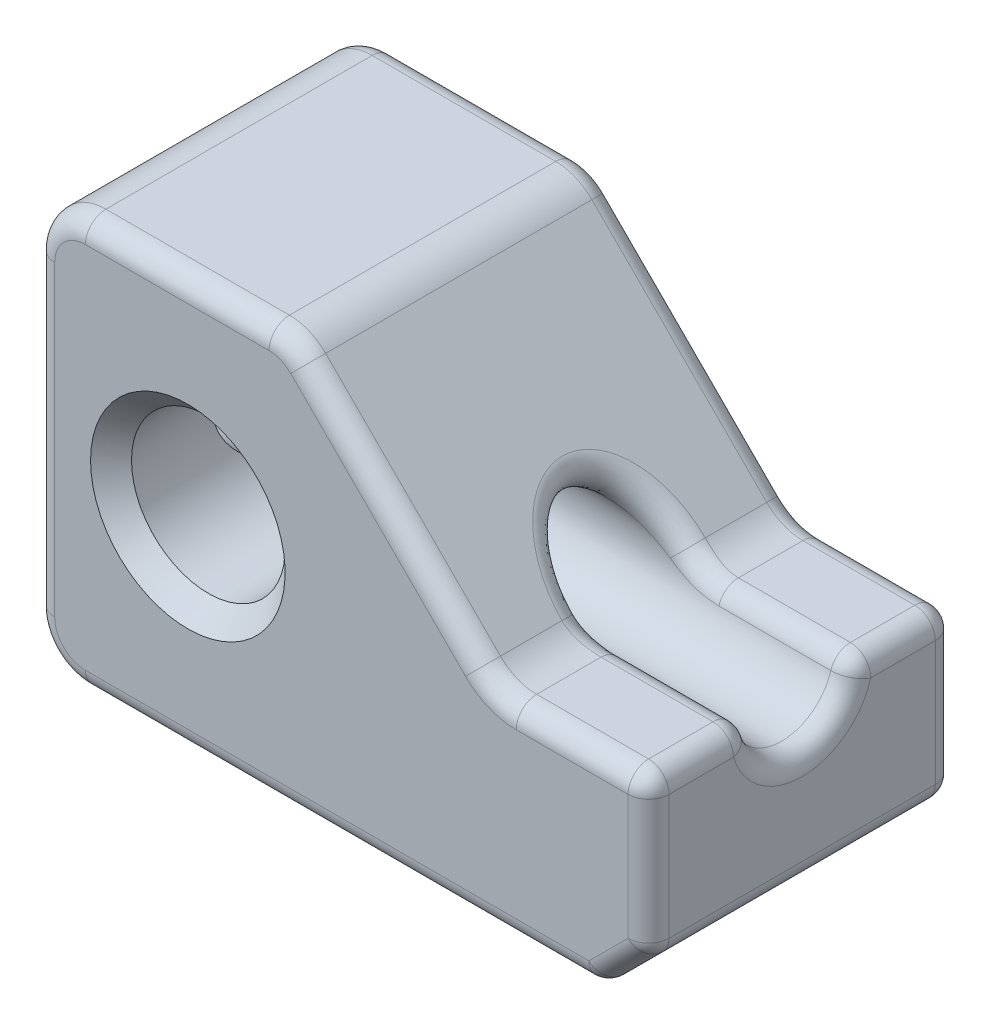
SolidWorks part; units mm, degrees
ref_plane "Front Plane" through (0, 0, 0) normal (0, 0, 1) x (1, 0, 0)
ref_plane "Top Plane" through (0, 0, 0) normal (0, 1, 0) x (1, 0, 0)
ref_plane "Right Plane" through (0, 0, 0) normal (1, 0, 0) x (0, 0, -1)
sketch "Sketch1" plane through (0, 0, 0) normal (0, 0, 1) x (1, 0, 0)
  line L0 (0, 0) -> (55, 0)
  line L1 (60, 5) -> (60, 20)
  line L2 (60, 20) -> (45, 20)
  line L3 (45, 20) -> (25, 40)
  line L4 (25, 40) -> (5, 40)
  line L5 (0, 35) -> (0, 0)
  line L6 (55, 0) -> (60, 5)
  circle A0 centre (15, 20) radius 7.5
  arc A1 (0, 35) -> (5, 40) centre (5, 35) cw
  point P1 (60, 0)
  point P11 (0, 40)
  dimension "D7" = 15
  dimension "D10" = 5
  dimension "D1" = 60
  dimension "D2" = 270
  dimension "D3" = 20
  dimension "D4" = 45
  dimension "D5" = 40
  dimension "D6" = 25
  dimension "D8" = 15
  dimension "D9" = 20
extrude "Boss-Extrude1" add sketch "Sketch1" along normal blind 15 and the other way blind 15
sketch "Sketch2" plane through (0, 0, 0) normal (-1, 0, 0) x (0, 0, 1)
  line L0 (-15, 0) -> (15, 0) construction
  circle A0 centre (0, 20) radius 5
  point P6 (-30.4016, 42.0063)
  dimension "D1" = 10
  dimension "D2" = 20
extrude "Cut-Extrude1" cut sketch "Sketch2" against normal up to surface (60 mm away) contours A0 up to face at (60, 12.5, 0)
fillet "Fillet1" radius 5 4 edges at (0, 0, 0) (45, 20, -10) (45, 20, 10) (25, 40, 0)
fillet "Fillet2" radius 2 32 edges at (24.8423, 39.6194, 15) (13.9645, 40, 15) (35, 30, 15) (1.4645, 38.5355, 15) (45.1577, 20.3806, 15) (0, 20, 15) (40, 25, 0) (53.5355, 20, 15) (44.7993, 20.5459, 4.9701) (1.4645, 1.4645, 15) (60, 12.5, 15) (45.4304, 20.2769, -4.9923) (60, 20, 10) (53.5355, 20, 5) (57.5, 2.5, 15) (30, 0, 15) (60, 5, 0) (53.5355, 20, -5) (60, 15, 0) (57.5, 2.5, -15) (55, 0, 0) (60, 12.5, -15) (60, 20, -10) (30, 0, -15) (53.5355, 20, -15) (1.4645, 1.4645, -15) (45.1577, 20.3806, -15) (0, 20, -15) (35, 30, -15) (1.4645, 38.5355, -15) (24.8423, 39.6194, -15) (13.9645, 40, -15)
chamfer "Chamfer1" distance 2 angle 45 2 edges at (22.5, 20, 15) (22.5, 20, -15)
chamfer "Chamfer2" distance 1 angle 45 1 edges at (0, 15, 0)
